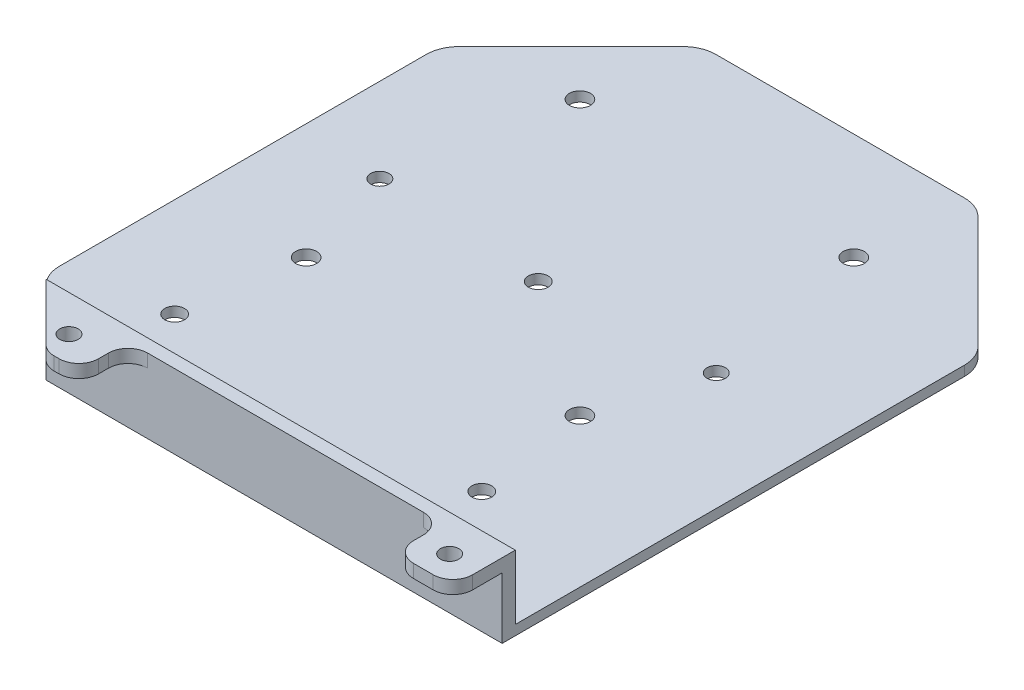
SolidWorks part; units mm, degrees
ref_plane "Front Plane" through (0, 0, 0) normal (0, 0, 1) x (1, 0, 0)
ref_plane "Top Plane" through (0, 0, 0) normal (0, 1, 0) x (1, 0, 0)
ref_plane "Right Plane" through (0, 0, 0) normal (1, 0, 0) x (0, 0, -1)
sketch "Croquis1" plane through (0, 0, 0) normal (0, 1, 0) x (1, 0, 0)
  line L0 (-38.5, -16.495) -> (43.5, -16.495)
  line L5 (-38.5, 74.005) -> (43.5, 74.005)
  line L6 (-38.5, 74.005) -> (-38.5, -25.995)
  line L7 (-38.5, -25.995) -> (43.5, -25.995)
  line L8 (43.5, 74.005) -> (43.5, -25.995)
  line L9 (-38.5, -18.495) -> (43.5, -18.495)
  circle A0 centre (-19, -21.995) radius 1.4
  circle A1 centre (39, -21.995) radius 1.4
  circle A2 centre (-25.63, 31.995) radius 1.4
  circle A3 centre (25.63, 31.995) radius 1.4
  point P0 (0, 0)
  point P1 (0, 0)
  dimension "D9" = 2.8
  dimension "D4" = 64.63
  dimension "D2" = 25.995
  dimension "D3" = 58
  dimension "D5" = 19
  dimension "D6" = 51.26
  dimension "D7" = 53.99
  dimension "D8" = 4
  dimension "D10" = 43.5
  dimension "D11" = 100
  dimension "D12" = 38.5
  dimension "D13" = 3.5
  dimension "D14" = 2
extrude "Saliente-Extruir1" add sketch "Croquis1" along normal blind 1.5 contours L8 L5 L6 L0 A3 A2 region at (2.5042, 0, -28.7496)
extrude "Saliente-Extruir2" add sketch "Croquis1<3>" along normal blind 9.31 separate body contours L6 L9 L8 L0 region at (2.5, 0, 17.495)
sketch "Croquis1<3>" plane through (0, 0, 0) normal (0, 1, 0) x (1, 0, 0) same geometry as "Croquis1"
extrude "Saliente-Extruir3" add sketch "Croquis1<4>" along normal blind 2 from surface contours L9 L6 L7 L8 A1 A0 | L6 L9 L8 L0 region at (2.5, 0, 17.495) region at (2.3467, 0, 22.2501) starting at face at (2.5, 9.31, 17.495)
sketch "Croquis1<4>" plane through (0, 0, 0) normal (0, 1, 0) x (1, 0, 0) same geometry as "Croquis1"
sketch "Croquis2" plane through (0, 1.5, 0) normal (0, 1, 0) x (1, 0, 0)
  line L3 (43.5, 74.005) -> (43.5, -16.495) construction
  line L4 (43.5, -16.495) -> (-38.5, -16.495) construction
  circle A0 centre (-23.4, -1.495) radius 1.5
  circle A1 centre (23.4, -1.495) radius 1.5
  circle A2 centre (0, 30.505) radius 1.5
  circle A3 centre (-20.86, 57.715) radius 1.6
  circle A4 centre (20.86, 57.715) radius 1.6
  circle A5 centre (20.86, 15.995) radius 1.6
  circle A6 centre (-20.86, 15.995) radius 1.6
  dimension "D1" = 3
  dimension "D7" = 3.2
  dimension "D2" = 46.8
  dimension "D3" = 23.4
  dimension "D4" = 32
  dimension "D6" = 41.72
  dimension "D8" = 41.72
  dimension "D9" = 22.64
  dimension "D10" = 32.49
  dimension "D5" = 15
extrude "Cortar-Extruir1" cut sketch "Croquis2" against normal blind 1.5
combine bodies "Combinar1" operation type add bodies to combine 105 102
sketch "Croquis3" plane through (0, 11.31, 0) normal (0, 1, 0) x (1, 0, 0)
  line L0 (-38.5, -5.995) -> (-18.5, -25.995)
  line L3 (-18.5, -25.995) -> (-38.5, -25.995)
  line L4 (-38.5, -25.995) -> (-38.5, -5.995)
  line L5 (-38.5, 74.005) -> (-38.5, 54.005)
  line L6 (-38.5, 54.005) -> (-18.5, 74.005)
  line L8 (-18.5, 74.005) -> (-38.5, 74.005)
  line L9 (43.5, 74.005) -> (23.5, 74.005)
  line L10 (23.5, 74.005) -> (43.5, 54.005)
  line L12 (43.5, 54.005) -> (43.5, 74.005)
  line L13 (-13.5, -25.995) -> (-13.5, -18.495)
  line L14 (-13.5, -18.495) -> (34.5, -18.495)
  line L15 (34.5, -18.495) -> (34.5, -25.995)
  line L16 (-13.5, -25.995) -> (34.5, -25.995)
  line L17 (43.5, -25.995) -> (43.5, -16.495) construction
  line L18 (43.5, -25.995) -> (-38.5, -25.995) construction
  line L19 (-38.5, -25.995) -> (-38.5, -16.495) construction
  line L20 (-38.5, 74.005) -> (-38.5, -16.495) construction
  line L21 (-38.5, 74.005) -> (43.5, 74.005) construction
  circle A0 centre (39, -21.995) radius 1.4 construction
  point P2 (-38.5, 35.995)
  point P4 (0, 0)
  point P5 (-38.5, -25.995)
  point P13 (43.5, 74.005)
  point P14 (23.5234, 74.005)
  point P19 (0, 0)
  point P20 (0, 0)
  point P27 (0, 0)
  point P28 (0, 0)
  point P29 (-13.5, -25.995)
  point P32 (0, 0)
  point P35 (-38.5, -25.995)
  point P37 (0, 0)
  point P38 (0, 0)
  point P40 (0, 0)
  point P41 (0, 0)
  point P42 (-38.5, 74.005)
  point P44 (0, 0)
  point P48 (23.5, 74.005)
  line M30 (-38.5, -16.495) -> (-38.5, -25.995)
  line M31 (-38.5, -25.995) -> (43.5, -25.995)
  line M33 (43.5, -16.495) -> (-38.5, -16.495)
  dimension "D9" = 3.5
  dimension "D1" = 45
  dimension "D2" = 20
  dimension "D3" = 45
  dimension "D4" = 45
  dimension "D5" = 20
  dimension "D6" = 20
  dimension "D7" = 48
  dimension "D8" = 9
extrude "Cortar-Extruir2" cut sketch "Croquis3" against normal through all contours L0 M33 M30 M31 | L4 L0 M33 | L15 L14 L13 M31 | L6 L8 L5 | L10 L12 L9 region at (10.5, 11.31, 22.245) region at (-35, 11.31, 12.995) region at (-30.6284, 11.31, 21.7382) region at (-31.8333, 11.31, -67.3383) region at (36.8333, 11.31, -67.3383)
fillet "Redondeo1" radius 5 5 edges at (43.5, 0.75, -54.005) (23.5, 0.75, -74.005) (-18.5, 0.75, -74.005) (-38.5, 0.75, -54.005) (-38.5, 0.75, 5.995)
fillet "Redondeo2" radius 3 6 edges at (34.5, 10.31, 18.495) (-13.5, 10.31, 18.495) (-13.5, 10.31, 25.995) (-18.5, 10.31, 25.995) (43.5, 10.31, 25.995) (34.5, 10.31, 25.995)
equation "\"D3@Croquis2\"=\"D2@Croquis2\"/2"
